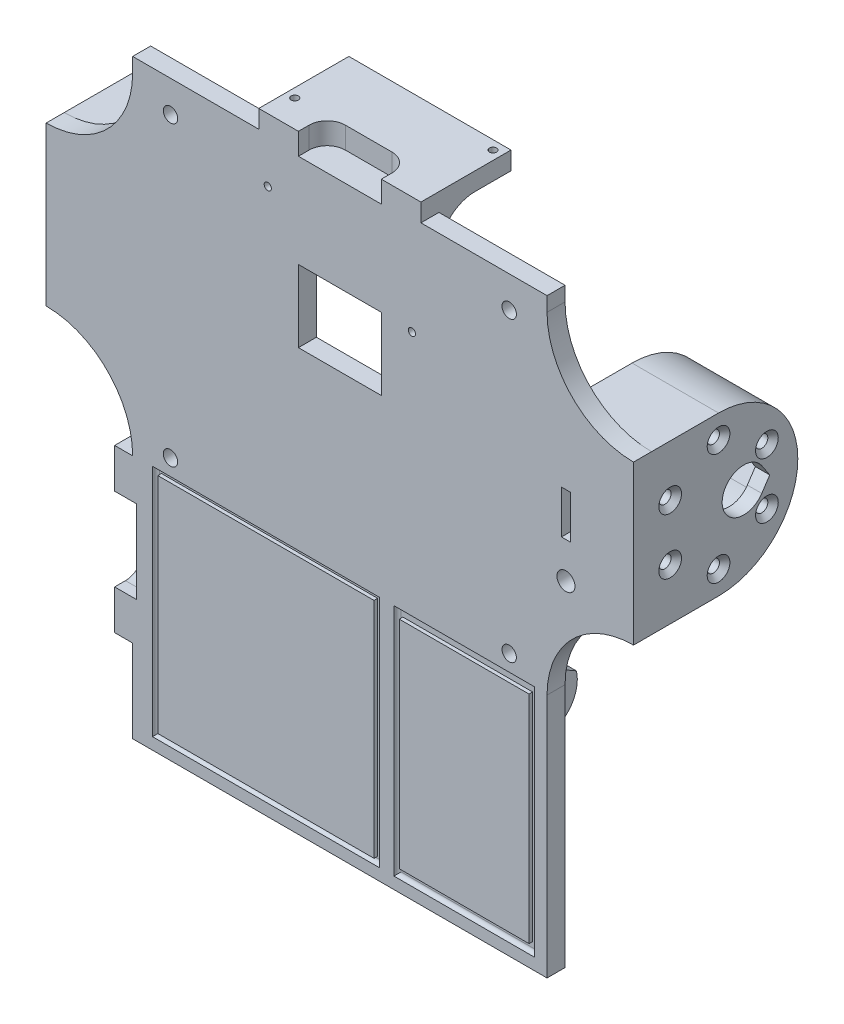
SolidWorks part; units mm, degrees
ref_plane "Front Plane" through (0, 0, 0) normal (0, 0, 1) x (1, 0, 0)
ref_plane "Top Plane" through (0, 0, 0) normal (0, 1, 0) x (1, 0, 0)
ref_plane "Right Plane" through (0, 0, 0) normal (1, 0, 0) x (0, 0, -1)
sketch "Sketch1" plane through (0, 0, 0) normal (0, 0, 1) x (1, 0, 0)
  line L0 (0, 0) -> (7, 5.25) construction
  line L1 (0, 0) -> (115, 0)
  line L2 (0, 0) -> (0, 100)
  line L3 (0, 100) -> (115, 100)
  line L4 (115, 0) -> (115, 100)
  line L5 (7, 94.75) -> (108, 94.75) construction
  line L6 (7, 94.75) -> (7, 5.25) construction
  line L7 (7, 5.25) -> (108, 5.25) construction
  line L8 (108, 94.75) -> (108, 5.25) construction
  line L9 (7, 94.75) -> (0, 100) construction
  line L10 (115, 100) -> (108, 94.75) construction
  line L11 (7, 94.75) -> (10.5, 91.25) construction
  line L12 (10.5, 91.25) -> (104.5, 91.25) construction
  line L13 (10.5, 91.25) -> (10.5, 8.75) construction
  line L14 (10.5, 8.75) -> (104.5, 8.75) construction
  line L15 (104.5, 91.25) -> (104.5, 8.75) construction
  line L16 (104.5, 91.25) -> (108, 94.75) construction
  line L17 (108, 5.25) -> (104.5, 8.75) construction
  line L18 (10.5, 8.75) -> (7, 5.25) construction
  circle A4 centre (10.5, 91.25) radius 2
  circle A5 centre (104.5, 91.25) radius 2
  circle A6 centre (104.5, 8.75) radius 2
  circle A7 centre (10.5, 8.75) radius 2
  dimension "D5" = 3.5
  dimension "D7" = 4
  dimension "D1" = 100
  dimension "D2" = 115
  dimension "D3" = 89.5
  dimension "D4" = 101
  dimension "D6" = 3.5
extrude "Boss-Extrude1" add sketch "Sketch1" along normal blind 5
sketch "Sketch2" plane through (0, 0, 5) normal (0, 0, 1) x (1, 0, 0)
  line L0 (115, 0) -> (115, 100) construction
  line L1 (0, 0) -> (115, 0)
  line L2 (0, 0) -> (0, -64)
  line L3 (0, -64) -> (115, -64)
  line L4 (115, 0) -> (115, -64)
  dimension "D1" = 64
extrude "Boss-Extrude2" add sketch "Sketch2" against normal up to surface (5 mm away) up to face at (106.5, 8.75, 0)
sketch "Sketch3" plane through (0, 0, 5) normal (0, 0, 1) x (1, 0, 0)
  line L0 (0, 100) -> (0, -64) construction
  line L1 (7, 2.75) -> (67, 2.75)
  line L2 (7, 2.75) -> (7, -59.25)
  line L3 (7, -59.25) -> (67, -59.25)
  line L4 (67, 2.75) -> (67, -59.25)
  line L5 (7, 2.75) -> (67, -59.25) construction
  line L6 (72.5, 4.25) -> (111.5, -60.75) construction
  line L7 (68.5, -60.75) -> (5.5, -60.75)
  line L8 (68.5, -60.75) -> (68.5, 4.25)
  line L9 (68.5, 4.25) -> (5.5, 4.25)
  line L10 (5.5, -60.75) -> (5.5, 4.25)
  line L11 (68.5, -60.75) -> (5.5, 4.25) construction
  line L12 (68.5, 4.25) -> (5.5, -60.75) construction
  line L13 (72.5, 4.25) -> (111.5, 4.25)
  line L14 (72.5, 4.25) -> (72.5, -60.75)
  line L15 (72.5, -60.75) -> (111.5, -60.75)
  line L16 (111.5, 4.25) -> (111.5, -60.75)
  line L18 (110, -58.25) -> (74, -58.25)
  line L19 (110, -58.25) -> (110, 1.75)
  line L20 (110, 1.75) -> (74, 1.75)
  line L21 (74, -58.25) -> (74, 1.75)
  line L22 (110, -58.25) -> (74, 1.75) construction
  line L23 (110, 1.75) -> (74, -58.25) construction
  circle A0 centre (10.5, 8.75) radius 2 construction
  point P8 (37, -28.25)
  point P17 (92, -28.25)
  point P18 (92, -28.25)
  dimension "D1" = 62
  dimension "D2" = 60
  dimension "D3" = 7
  dimension "D4" = 6
  dimension "D5" = 1.5
  dimension "D6" = 1.5
  dimension "D7" = 1.5
  dimension "D8" = 2.5
  dimension "D9" = 4
sketch "Sketch4" plane through (0, 100, 0) normal (0, 1, 0) x (1, 0, 0)
  line L0 (115, -5) -> (0, -5) construction
  line L2 (80, -5) -> (80, 20)
  line L3 (80, 20) -> (35, 20)
  line L4 (35, -5) -> (35, 20)
  line L5 (57.5, -5) -> (35, 20) construction
  line L6 (80, 20) -> (57.5, -5) construction
  line L7 (115, 0) -> (0, 0) construction
  line L8 (35, -5) -> (80, -5)
  line L9 (115, -5) -> (115, 0) construction
  point P0 (57.5, -5)
  dimension "D1" = 20
  dimension "D2" = 45
extrude "Boss-Extrude3" add sketch "Sketch4" along normal blind 5
sketch "Sketch5" plane through (0, 105, 0) normal (0, 1, 0) x (1, 0, 0)
  line L1 (0, 0) -> (115, 0) construction
  line L2 (35, 20) -> (35, -5) construction
  line L3 (80, -5) -> (80, 20) construction
  line L5 (80, 20) -> (35, 20) construction
  line L6 (35, 20) -> (46, -5) construction
  line L7 (46, 0) -> (69, 0) construction
  line L8 (46, 0) -> (46, -5) construction
  line L9 (46, -5) -> (69, -5) construction
  line L10 (69, 0) -> (69, -5) construction
  line L11 (69, -5) -> (80, 20) construction
  line L12 (35, -5) -> (80, -5) construction
  circle A0 centre (37.5, 2.5) radius 1
  circle A1 centre (77.5, 17.5) radius 1
  dimension "D5" = 2
  dimension "D1" = 2.5
  dimension "D2" = 2.5
  dimension "D3" = 2.5
  dimension "D4" = 2.5
  dimension "D6" = 5
  dimension "D7" = 23
extrude "Cut-Extrude2" cut sketch "Sketch5" against normal through all
fillet "Fillet1" radius 10 1 edges at (57.5, 100, 0)
sketch "Sketch6" plane through (0, 100, 0) normal (0, -1, 0) x (1, 0, 0)
  circle A0 centre (37.5, -2.5) radius 2.25
  dimension "D1" = 4.5
extrude "Cut-Extrude3" cut sketch "Sketch6" along normal through all
sketch "Sketch7" plane through (0, 105, 0) normal (0, 1, 0) x (1, 0, 0)
  line L1 (46, 3) -> (69, 3)
  line L2 (46, 3) -> (46, -5)
  line L3 (46, -5) -> (69, -5)
  line L4 (69, 3) -> (69, -5)
  dimension "D1" = 8
extrude "Cut-Extrude4" cut sketch "Sketch7" against normal blind 6
sketch "Sketch8" plane through (0, 0, 0) normal (0, 0, -1) x (-1, 0, 0)
  line L0 (-35, 90) -> (-35, 100) construction
  line L1 (-80, 90) -> (-35, 90) construction
  line L2 (-80, 90) -> (-80, 70) construction
  line L3 (-80, 70) -> (-35, 70) construction
  line L4 (-35, 90) -> (-35, 70) construction
  line L5 (-80, 70) -> (-69, 53) construction
  line L6 (-69, 73) -> (-46, 73)
  line L7 (-69, 73) -> (-69, 53)
  line L8 (-69, 53) -> (-46, 53)
  line L9 (-46, 73) -> (-46, 53)
  line L10 (-46, 53) -> (-35, 70) construction
  circle A0 centre (-37.5, 87.5) radius 1
  circle A1 centre (-77.5, 72.5) radius 1
  dimension "D2" = 2
  dimension "D3" = 2.5
  dimension "D5" = 2.5
  dimension "D1" = 20
  dimension "D4" = 2.5
  dimension "D6" = 2.5
  dimension "D7" = 23
  dimension "D8" = 20
  dimension "D9" = 3
extrude "Cut-Extrude5" cut sketch "Sketch8" against normal through all
ref_plane "Plane1" through (57.5, 0, 0) normal (-1, 0, 0) x (0, 0, 1)
sketch "Sketch9" plane through (115, 0, 0) normal (1, 0, 0) x (0, 0, -1)
  line L0 (0, 0) -> (0, 28) construction
  line L2 (0, 50) -> (18.6, 50) construction
  line L4 (18.6, 72) -> (0, 72)
  line L6 (18.6, 28) -> (0, 28)
  line L8 (-5, -64) -> (-5, 100) construction
  line L9 (0, 72) -> (-5, 72)
  line L11 (0, 28) -> (-5, 28)
  line L13 (-5, 72) -> (-5, 28)
  circle A0 centre (18.6, 50) radius 18.5
  arc A1 (18.6, 28) -> (18.6, 72) centre (18.6, 50) ccw
  dimension "D2" = 37
  dimension "D3" = 44
  dimension "D1" = 50
  dimension "D4" = 18.6
extrude "Boss-Extrude4" add sketch "Sketch9" along normal blind 20 separate body
sketch "Sketch10" plane through (135, 0, 0) normal (1, 0, 0) x (0, 0, -1)
  line L0 (18.6, 50) -> (34.1, 50) construction
  line L1 (32.0234, 57.75) -> (18.6, 50) construction
  line L2 (-5, 28) -> (18.6, 28) construction
  line L4 (18.6, 72) -> (-5, 72) construction
  line L5 (-5, 28) -> (18.6, 28)
  line L6 (-5, 72) -> (-5, 28)
  line L7 (18.6, 72) -> (-5, 72)
  circle A2 centre (18.6, 50) radius 18.5 construction
  circle A3 centre (18.6, 50) radius 18.5 construction
  circle A4 centre (25.6, 50) radius 6
  circle A5 centre (18.6, 50) radius 15.5 construction
  arc A6 (18.6, 28) -> (18.6, 72) centre (18.6, 50) ccw
  point P11 (32.0234, 57.75)
  point P17 (32.0234, 42.25)
  point P18 (18.6, 34.5)
  point P19 (5.1766, 42.25)
  point P20 (5.1766, 57.75)
  point P21 (18.6, 65.5)
  point P22 (18.6, 50)
  dimension "D1" = 12
  dimension "D3" = 31
  dimension "D2" = 7
  dimension "D4" = 30
  dimension "D5" = 6
extrude "Boss-Extrude5" add sketch "Sketch10" along normal blind 4
hole_wizard "CSK for M3 Flat Head Machine Screw1" positions "Sketch11" profile "Sketch12" countersink size "M3" standard "ANSI Metric" end condition through all
sketch "Sketch11" plane through (139, 0, 0) normal (1, 0, 0) x (0, 0, -1)
  point P0 (32.0234, 57.75)
  point P3 (18.6, 65.5)
  point P6 (5.1766, 57.75)
  point P9 (5.1766, 42.25)
  point P12 (18.6, 34.5)
  point P15 (32.0234, 42.25)
sketch "Sketch12" plane through (139, 57.75, -32.0234) normal (0, 1, 0) x (0, 0, -1)
  line L0 (0, 0) -> (0, 139)
  line L1 (0, 139) -> (1.7, 139)
  line L2 (1.7, 139) -> (1.7, 1.45)
  line L3 (1.7, 1.45) -> (3.15, 0)
  line L5 (3.15, 0) -> (0, 0)
  line L6 (-1.7, 1.45) -> (-3.15, 0) construction
  line L11 (0, -6.35) -> (0, 107.95) construction
  dimension "Thru Hole Dia." = 3.4
  dimension "Thru Hole Depth" = 139
  dimension "Near C'Sink Dia." = 6.3
  dimension "Near C'Sink Angle" = 90
mirror "Mirror10" about plane through (57.5, 0, 0) normal (-1, 0, 0) of "CSK for M3 Flat Head Machine Screw1", "Boss-Extrude5", "Boss-Extrude4"
sketch "Sketch15" plane through (0, 0, 0) normal (0, 0, -1) x (-1, 0, 0)
  line L0 (-139, 72) -> (-115, 72) construction
  line L1 (-115, -64) -> (-115, 100) construction
  line L2 (-139, 28) -> (-115, 28) construction
  line L3 (0, 28) -> (0, -64) construction
  line L4 (24, 28) -> (0, 28) construction
  line L5 (0, 100) -> (0, 72) construction
  line L6 (24, 72) -> (0, 72) construction
  line L7 (24, 72) -> (0, 72)
  line L8 (0, 72) -> (0, 96)
  line L9 (24, 28) -> (0, 28)
  line L10 (0, 28) -> (0, 4)
  line L11 (-115, 4) -> (-115, 28)
  line L12 (-115, 28) -> (-115, 72) construction
  line L13 (-115, 28) -> (-139, 28)
  line L14 (-115, 96) -> (-115, 72)
  line L15 (-115, 72) -> (-139, 72)
  arc A0 (-139, 72) -> (-115, 96) centre (-139, 96) ccw
  arc A1 (-115, 4) -> (-139, 28) centre (-139, 4) ccw
  arc A2 (0, 96) -> (24, 72) centre (24, 96) ccw
  arc A3 (24, 28) -> (0, 4) centre (24, 4) ccw
extrude "Boss-Extrude6" add sketch "Sketch15" against normal up to surface (5 mm away) up to face at (36.5, 87.5, 5)
ref_plane "Plane2" through (50.4, 0, 0) normal (-1, 0, 0) x (0, 0, 1)
sketch "Sketch16" plane through (50.4, 0, 0) normal (-1, 0, 0) x (0, 0, 1)
  line L0 (0, -9.5117) -> (-32.8318, -28.4672)
  line L1 (0, 4) -> (0, -64) construction
  line L2 (0, -9.5117) -> (0, -24.5117)
  line L3 (0, -24.5117) -> (-28.1738, -40.7779)
  line L4 (0, -17.0117) -> (-34.35, -36.8437) construction
  line L5 (-32.8318, -28.4672) -> (-43.5456, -34.6528)
  line L6 (-28.1738, -40.7779) -> (-37.0504, -45.9028)
  circle A0 centre (-34.35, -36.8437) radius 3.5
  arc A2 (-43.5456, -34.6528) -> (-37.0504, -45.9028) centre (-34.35, -36.8437) ccw
  dimension "D4" = 7
  dimension "D1" = 15
  dimension "D2" = 120
  dimension "D3" = 34.35
extrude "Boss-Extrude7" add sketch "Sketch16" along normal blind 10
mirror "Mirror11" about plane through (57.5, 0, 0) normal (-1, 0, 0) of "Boss-Extrude7"
fillet "Fillet3" radius 20 2 edges at (40.4, -17.0117, 0) (74.6, -17.0117, 0)
fillet "Fillet4" radius 5 4 edges at (35.4, -24.5117, 0) (79.6, -24.5117, 0) (35.4, -9.5117, 0) (79.6, -9.5117, 0)
sketch "Sketch19" plane through (0, 0, 0) normal (-1, 0, 0) x (0, 0, 1)
  line L0 (5, 4) -> (-20, 4)
  line L1 (-20, 4) -> (-20, -41)
  line L2 (5, -41) -> (-20, -41)
  line L3 (5.2881, -18.5) -> (-20, -41) construction
  line L4 (-20, 4) -> (5.2881, -18.5) construction
  line L5 (5, -41) -> (5, 4)
  line L8 (5, 4) -> (0, 4) construction
  line L9 (5, 4) -> (5, -64) construction
  point P0 (5.2881, -18.5)
  dimension "D1" = 45
  dimension "D2" = 25
extrude "Boss-Extrude9" add sketch "Sketch19" along normal blind 5
sketch "Sketch20" plane through (-5, 0, 0) normal (-1, 0, 0) x (0, 0, 1)
  line L0 (-20, 4) -> (-20, -41) construction
  line L1 (5, 4) -> (-20, 4) construction
  line L2 (0, -41) -> (0, -64) construction
  line L3 (-20, -41) -> (5, -41) construction
  circle A0 centre (-17.5, 1.5) radius 1
  circle A1 centre (-2.5, -38.5) radius 1
  dimension "D2" = 2.5
  dimension "D3" = 2
  dimension "D1" = 2.5
  dimension "D4" = 2.5
  dimension "D5" = 2.5
extrude "Cut-Extrude6" cut sketch "Sketch20" against normal up to surface (5 mm away) up to face at (0, -18.5, -10)
fillet "Fillet5" radius 10 1 edges at (0, -18.5, 0)
sketch "Sketch21" plane through (-5, 0, 0) normal (-1, 0, 0) x (0, 0, 1)
  line L0 (5, -41) -> (5, 4) construction
  line L1 (5, -7) -> (-3, -7)
  line L2 (5, -7) -> (5, -30)
  line L3 (5, -30) -> (-3, -30)
  line L4 (-3, -7) -> (-3, -30)
  line L5 (5, 4) -> (-3, -7) construction
  line L6 (5, -41) -> (-3, -30) construction
  dimension "D1" = 8
  dimension "D2" = 23
extrude "Cut-Extrude7" cut sketch "Sketch21" against normal blind 6
sketch "Sketch22" plane through (0, 0, 0) normal (1, 0, 0) x (0, 0, -1)
  circle A0 centre (2.5, -38.5) radius 2.25
  dimension "D1" = 4.5
extrude "Cut-Extrude8" cut sketch "Sketch22" along normal blind 15
sketch "Sketch23" plane through (0, 0, 5) normal (0, 0, 1) x (1, 0, 0)
  line L0 (139, 72) -> (147, 56) construction
  line L1 (117, 44) -> (117, 56) construction
  line L2 (117, 44) -> (147, 44) construction
  line L3 (147, 44) -> (147, 56) construction
  line L4 (117, 56) -> (147, 56) construction
  line L5 (139, 28) -> (147, 44) construction
  line L6 (119, 44) -> (120.25, 34) construction
  line L7 (139, 72) -> (139, 28) construction
  line L8 (121.5, 44) -> (121.5, 56)
  line L9 (121.5, 44) -> (119, 44)
  line L10 (119, 44) -> (119, 56)
  line L11 (121.5, 56) -> (119, 56)
  line L12 (120.25, 34) -> (121.5, 44) construction
  circle A0 centre (120.25, 34) radius 2.5
  dimension "D6" = 5
  dimension "D1" = 30
  dimension "D2" = 12
  dimension "D3" = 20
  dimension "D4" = 2.5
  dimension "D5" = 4.5
  dimension "D7" = 10
extrude "Cut-Extrude10" cut sketch "Sketch23" against normal blind 22
extrude "Cut-Extrude11" cut sketch "Sketch3" against normal blind 1
fillet "Fillet6" radius 1 8 edges at (37, -60.75, 4) (68.5, -28.25, 4) (37, 4.25, 4) (5.5, -28.25, 4) (92, -60.75, 4) (111.5, -28.25, 4) (92, 4.25, 4) (72.5, -28.25, 4)
fillet "Fillet7" radius 5 4 edges at (69, 102, -3) (46, 102, -3) (-2, -7, -3) (-2, -30, -3)
sketch "Sketch24" plane through (115, 0, 0) normal (-1, 0, 0) x (0, 0, 1)
  line L0 (-18.6, 50) -> (-55.3503, 50) construction
  line L1 (-35.057, 41.5491) -> (-39.3966, 50)
  line L2 (-39.3966, 50) -> (-35.057, 58.4509)
  circle A0 centre (-18.6, 50) radius 18.5 construction
  arc A1 (-35.057, 58.4509) -> (-35.057, 41.5491) centre (-18.6, 50) ccw
  dimension "D1" = 9.5
extrude "Cut-Extrude12" cut sketch "Sketch24" against normal up to surface (20 mm away) up to face at (135, 57.75, -33.7234)
sketch "Sketch25" plane through (135, 0, 0) normal (-1, 0, 0) x (0, 0, 1)
  line L0 (-25.6, 50) -> (-44.9333, 50) construction
  line L1 (-30.5923, 46.6718) -> (-32.8111, 50)
  line L6 (-32.8111, 50) -> (-30.5923, 53.3282)
  circle A0 centre (-25.6, 50) radius 6 construction
  arc A3 (-30.5923, 53.3282) -> (-30.5923, 46.6718) centre (-25.6, 50) ccw
  dimension "D2" = 4
extrude "Cut-Extrude13" cut sketch "Sketch25" against normal through all
mirror "Mirror14" about plane through (57.5, 0, 0) normal (-1, 0, 0) of "Cut-Extrude13"
sketch "Sketch26" plane through (0, 0, 0) normal (1, 0, 0) x (0, 0, -1)
  line L0 (35.057, 58.4509) -> (39.3966, 50) construction
  line L1 (39.3966, 50) -> (35.057, 41.5491) construction
  line L2 (35.057, 58.4509) -> (39.3966, 50)
  line L3 (39.3966, 50) -> (35.057, 41.5491)
  arc A0 (35.057, 41.5491) -> (35.057, 58.4509) centre (18.6, 50) ccw
extrude "Cut-Extrude14" cut sketch "Sketch26" against normal up to surface (20 mm away) up to face at (-20, 50, -37.1)
sketch "Sketch27" plane through (74.6, 0, 0) normal (1, 0, 0) x (0, 0, -1)
  line L0 (34.35, -36.8437) -> (51.856, -36.8437) construction
  line L1 (36.6548, -39.4777) -> (39.6651, -36.8437)
  line L2 (39.6651, -36.8437) -> (36.6548, -34.2097)
  circle A0 centre (34.35, -36.8437) radius 3.5 construction
  arc A1 (36.6548, -39.4777) -> (36.6548, -34.2097) centre (34.35, -36.8437) ccw
  dimension "D1" = 4
extrude "Cut-Extrude15" cut sketch "Sketch27" against normal up to surface (34.2 mm away) up to face at (40.4, -34.7414, -30.7086)
